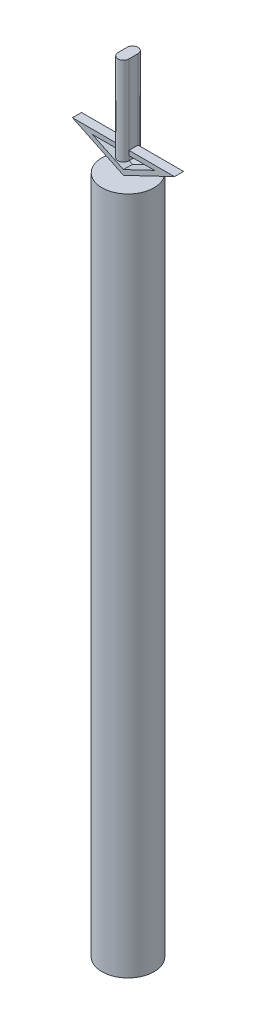
SolidWorks part; units mm, degrees
ref_plane "Front Plane" through (0, 0, 0) normal (0, 0, 1) x (1, 0, 0)
ref_plane "Top Plane" through (0, 0, 0) normal (0, 1, 0) x (1, 0, 0)
ref_plane "Right Plane" through (0, 0, 0) normal (1, 0, 0) x (0, 0, -1)
sketch "Sketch2" plane through (0, 0, 0) normal (0, 1, 0) x (1, 0, 0)
  circle A0 centre (0, 0) radius 11.5
  dimension "D1" = 23
extrude "Boss-Extrude1" add sketch "Sketch2" along normal blind 300
sketch "Sketch3" plane through (0, 0, 0) normal (0, 0, 1) x (1, 0, 0)
  line L0 (0, 300) -> (-22.5569, 310.779)
  line L1 (11.5, 300) -> (-11.5, 300) construction
  line L2 (-22.5569, 310.779) -> (22.5569, 310.779)
  line L3 (22.5569, 310.779) -> (0, 300)
  line L4 (0, 302.2166) -> (-13.7329, 308.779)
  line L5 (-13.7329, 308.779) -> (13.7329, 308.779)
  line L6 (13.7329, 308.779) -> (0, 302.2166)
  point P5 (28.8466, 513.6559)
  point P6 (24.2437, 509.6283)
  dimension "D1" = 25
  dimension "D2" = 25
  dimension "D3" = 2
extrude "Boss-Extrude2" add sketch "Sketch3" along normal blind 2 and the other way blind 2 separate body
sketch "Sketch6" plane through (0, 310.779, 0) normal (0, 1, 0) x (1, 0, 0)
  line L0 (0, 2) -> (0, -2) construction
  line L1 (22.5569, 2) -> (-22.5569, 2) construction
  line L2 (22.5569, -2) -> (-22.5569, -2) construction
  line L3 (2.4264, 2) -> (2.4264, -2)
  line L4 (-2.4264, 2) -> (-2.4264, -2)
  arc A0 (2.4264, 2) -> (-2.4264, 2) centre (0, 2) ccw
  arc A1 (-2.4264, -2) -> (2.4264, -2) centre (0, -2) ccw
  point P6 (0, 0)
extrude "Boss-Extrude5" add sketch "Sketch6" along normal blind 35 and the other way blind 4
